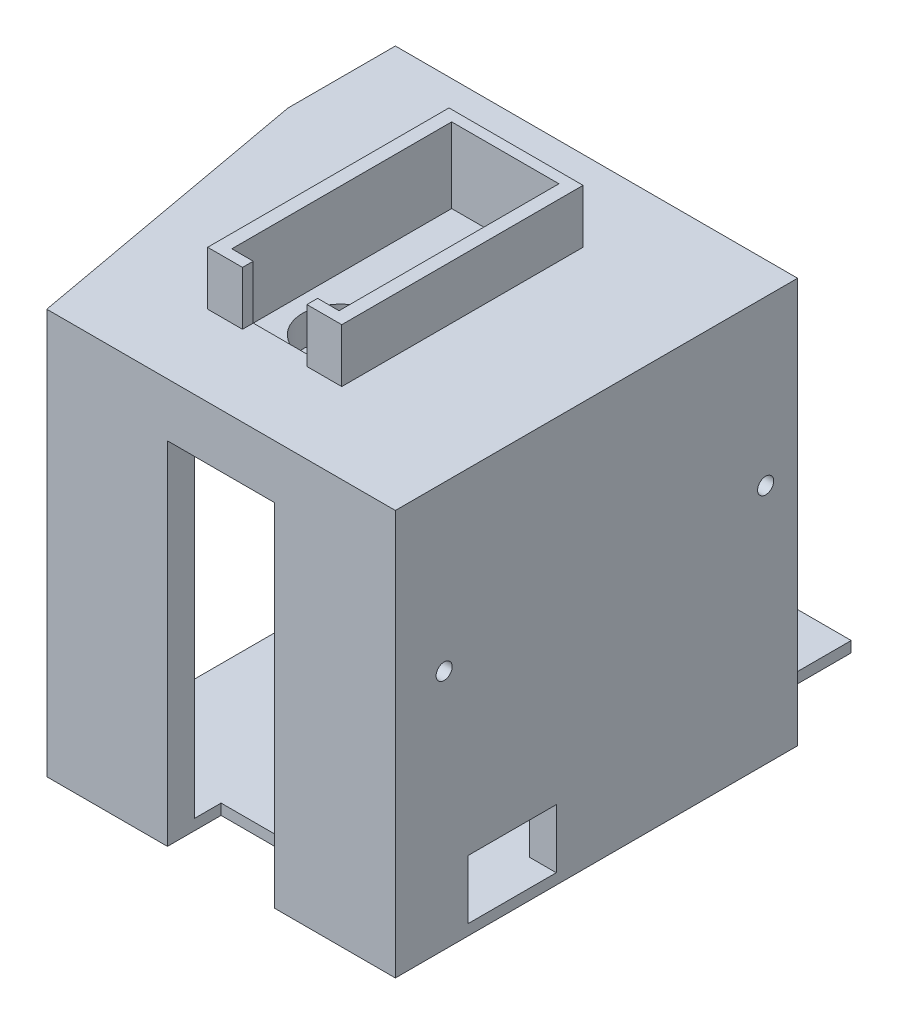
SolidWorks part; units mm, degrees
ref_plane "Front Plane" through (0, 0, 0) normal (0, 0, 1) x (1, 0, 0)
ref_plane "Top Plane" through (0, 0, 0) normal (0, 1, 0) x (1, 0, 0)
ref_plane "Right Plane" through (0, 0, 0) normal (1, 0, 0) x (0, 0, -1)
sketch "Sketch1" plane through (0, 0, 0) normal (0, 1, 0) x (1, 0, 0)
  line L1 (0, 0) -> (55, 0)
  line L2 (0, 0) -> (0, 65)
  line L3 (0, 65) -> (55, 65)
  line L4 (55, 0) -> (55, 65)
  dimension "D1" = 55
  dimension "D2" = 65
extrude "Base" add sketch "Sketch1" along normal blind 2
sketch "Sketch2" plane through (0, 2, 0) normal (0, 1, 0) x (1, 0, 0)
  line L0 (0, 0) -> (55, 0) construction
  line L2 (55, 65) -> (0, 65) construction
  circle A0 centre (3, 3.5) radius 1.2
  circle A1 centre (52, 3.5) radius 1.2
  circle A2 centre (3, 61.5) radius 1.2
  circle A3 centre (52, 61.5) radius 1.2
  point P12 (27.5, 0)
  dimension "D1" = 2.4
  dimension "D2" = 24.5
  dimension "D3" = 24.5
  dimension "D4" = 58
  dimension "D5" = 3.5
extrude "PiMountScrewHoles" cut sketch "Sketch2" against normal up to surface (2 mm away) up to face at (27.5, 0, -32.5)
sketch "Sketch3" plane through (0, 0, 0) normal (-1, 0, 0) x (0, 0, 1)
  line L0 (-65, 0) -> (0, 0) construction
  line L1 (-65, 2) -> (-45, 2)
  line L2 (-65, 2) -> (-65, 0)
  line L3 (-65, 0) -> (-45, 0)
  line L4 (-45, 2) -> (-45, 0)
  dimension "D1" = 20
extrude "PlateLegExt-1" add sketch "Sketch3" along normal blind 10
sketch "Sketch19" plane through (0, 0, -65) normal (0, 0, -1) x (-1, 0, 0)
  line L1 (-55, 2) -> (0, 2)
  line L2 (-55, 2) -> (-55, 0)
  line L3 (-55, 0) -> (0, 0)
  line L4 (0, 2) -> (0, 0)
extrude "PiFrontBase" add sketch "Sketch19" along normal blind 20
sketch "Sketch21" plane through (55, 0, 0) normal (1, 0, 0) x (0, 0, -1)
  line L0 (0, 0) -> (85, 0) construction
  line L1 (0, 2) -> (65, 2)
  line L2 (0, 2) -> (0, 0)
  line L3 (0, 0) -> (65, 0)
  line L4 (65, 2) -> (65, 0)
extrude "BatteryWall-Ext" add sketch "Sketch21" along normal blind 10
sketch "Sketch22" plane through (0, 0, 0) normal (0, 0, 1) x (1, 0, 0)
  line L0 (0, 0) -> (65, 0) construction
  line L1 (0, 2) -> (22.5, 2)
  line L2 (0, 2) -> (0, 0)
  line L3 (0, 0) -> (22.5, 0)
  line L4 (22.5, 2) -> (22.5, 0)
  line L6 (42.5, 2) -> (55, 2)
  line L7 (42.5, 2) -> (42.5, 0)
  line L8 (42.5, 0) -> (55, 0)
  line L11 (0, 2) -> (65, 2) construction
  line L12 (55, 2) -> (55, 0)
  line L13 (55, 0) -> (55, 2) construction
  point P16 (32.5, 0)
  dimension "D1" = 10
  dimension "D2" = 20
extrude "PlateLegExt-2" add sketch "Sketch22" along normal blind 10
sketch "Sketch30" plane through (55, 0, 0) normal (1, 0, 0) x (0, 0, -1)
  line L1 (-10, 2) -> (0, 2)
  line L2 (-10, 2) -> (-10, 0)
  line L3 (-10, 0) -> (0, 0)
  line L4 (0, 2) -> (0, 0)
extrude "CornerExtension" add sketch "Sketch30" along normal up to vertex (10 mm away) up to point (65, 2, 0)
sketch "Sketch23" plane through (0, 2, 0) normal (0, 1, 0) x (1, 0, 0)
  line L0 (65, 65) -> (55, 65) construction
  line L2 (22.5, -5) -> (0, -5)
  line L3 (22.5, -5) -> (22.5, -10)
  line L4 (-5, 65) -> (-10, 65)
  line L8 (60, 65) -> (65, 65)
  line L9 (60, 65) -> (60, -5)
  line L11 (65, 65) -> (65, -10)
  line L14 (-5, 65) -> (-5, 45)
  line L15 (-5, 45) -> (-10, 45)
  line L16 (-10, 65) -> (-10, 45)
  line L21 (22.5, -10) -> (0, -10)
  line L22 (0, -5) -> (0, -10)
  line L23 (22.5, -10) -> (22.5, 0) construction
  line L24 (0, 65) -> (-10, 65) construction
  line L25 (42.5, -10) -> (42.5, 0) construction
  line L26 (42.5, -10) -> (65, -10)
  line L27 (42.5, -10) -> (42.5, -5)
  line L30 (65, 65) -> (65, -10) construction
  line L31 (65, -10) -> (42.5, -10) construction
  line L32 (42.5, -5) -> (60, -5)
extrude "PlateLegs" add sketch "Sketch23" along normal blind 63.5
sketch "Sketch29" plane through (65, 0, 0) normal (1, 0, 0) x (0, 0, -1)
  line L0 (-10, 0) -> (65, 0) construction
  circle A0 centre (59.045, 45) radius 1.5
  circle A1 centre (-0.905, 45) radius 1.5
  point P8 (27.5, 0)
  dimension "D1" = 3
  dimension "D2" = 59.95
  dimension "D3" = 31.545
  dimension "D4" = 45
extrude "Battery-ScrewHoles" cut sketch "Sketch29" against normal up to surface (5 mm away) up to face at (60, 33.75, -30)
sketch "Sketch24" plane through (0, 65.5, 0) normal (0, 1, 0) x (1, 0, 0)
  line L7 (0, -10) -> (65, -10)
  line L8 (42.5, -10) -> (65, -10) construction
  line L9 (65, -10) -> (65, 65)
  line L10 (65, 65) -> (-10, 65)
  line L11 (-10, 65) -> (-10, 45)
  line L12 (-10, 45) -> (0, -10)
extrude "RotatorPlate" add sketch "Sketch24" along normal blind 10
sketch "Sketch25" plane through (0, 75.5, 0) normal (0, 1, 0) x (1, 0, 0)
  line L2 (37.5, 7) -> (37.5, 48)
  line L4 (17.5, 7) -> (17.5, 48)
  line L7 (37.5, 48) -> (17.5, 48)
  line L8 (17.5, 7) -> (37.5, 7)
  line L9 (65, -10) -> (65, 65) construction
  line L11 (65, 65) -> (-10, 65) construction
  point P8 (27.5, 65)
  point P9 (65, 27.5)
  point P10 (37.5, 27.5)
  point P11 (27.5, 48)
  dimension "D1" = 41
  dimension "D2" = 20
extrude "Inset-Servo" cut sketch "Sketch25" against normal blind 4
sketch "Sketch26" plane through (0, 71.5, 0) normal (0, 1, 0) x (1, 0, 0)
  line L0 (17.5, 7) -> (37.5, 7) construction
  line L3 (37.5, 48) -> (17.5, 48) construction
  circle A0 centre (27.5, 17.25) radius 1.5
  point P8 (27.5, 48)
  dimension "D1" = 3
  dimension "D2" = 10.25
extrude "Hole-ServoScrew" cut sketch "Sketch26" against normal up to surface (6 mm away) up to face at (20.9091, 65.5, -15.4545)
sketch "Sketch27" plane through (0, 71.5, 0) normal (0, 1, 0) x (1, 0, 0)
  circle A0 centre (27.5, 17.25) radius 7
  circle A1 centre (27.5, 17.25) radius 1.5 construction
  dimension "D1" = 14
extrude "Inset-ServoAxle" cut sketch "Sketch27" against normal blind 5.8
sketch "Sketch28" plane through (0, 75.5, 0) normal (0, 1, 0) x (1, 0, 0)
  line L2 (37.5, 7) -> (37.5, 48)
  line L4 (17.5, 7) -> (17.5, 48)
  line L6 (40, 5) -> (40, 50)
  line L8 (15, 5) -> (15, 50)
  line L11 (37.5, 7) -> (37.5, 48) construction
  line L18 (17.5, 48) -> (17.5, 7) construction
  line L19 (15, 5) -> (21.5, 5)
  line L24 (21.5, 5) -> (21.5, 7)
  line L25 (17.5, 7) -> (37.5, 7) construction
  line L26 (40, 5) -> (33.5, 5)
  line L27 (33.5, 5) -> (33.5, 7)
  line L28 (17.5, 7) -> (37.5, 7) construction
  line L29 (33.5, 7) -> (37.5, 7)
  line L30 (17.5, 7) -> (21.5, 7)
  line L31 (17.5, 48) -> (37.5, 48)
  line L32 (15, 50) -> (40, 50)
  line L33 (37.5, 48) -> (17.5, 48) construction
  point P15 (27.5, 7)
  point P20 (40, 27.5)
  point P21 (37.5, 27.5)
  dimension "D7" = 6
  dimension "D1" = 2.5
  dimension "D3" = 45
  dimension "D4" = 25
  dimension "D8" = 12
extrude "RetainingWalls-Servo" add sketch "Sketch28" along normal blind 10
sketch "PowerPlug-EdgeLine" plane through (0, 2, 0) normal (0, 1, 0) x (1, 0, 0)
  line L1 (52, 3.5) -> (60, 3.5) construction
  line L3 (60, 65) -> (60, -5) construction
sketch "Sketch31" plane through (60, 0, 0) normal (-1, 0, 0) x (0, 0, 1)
  line L0 (-65, 2) -> (5, 2) construction
  line L1 (-20, 13) -> (-3.5, 13)
  line L2 (-20, 13) -> (-20, 2)
  line L3 (-20, 2) -> (-3.5, 2)
  line L4 (-3.5, 13) -> (-3.5, 2)
  line L6 (5, 65.5) -> (5, 2) construction
  point P8 (0, 0)
  point P9 (-3.4479, 2)
  point P10 (0, 0)
  dimension "D2" = 11
  dimension "D3" = 25
extrude "Power-Hole" cut sketch "Sketch31" against normal up to surface (5 mm away) up to face at (65, 45, -60.545)
equation "\"PlateLegExtent\"= 10mm"
equation "\"D1@PlateLegExt-1\" = \"PlateLegExtent\""
equation "\"PlateLegHeight\"= 2.5in"
equation "\"D1@BatteryWall-Ext\" = \"PlateLegExtent\""
equation "\"D1@PlateLegExt-2\" = \"PlateLegExtent\""
equation "\"D1@PlateLegs\" = \"PlateLegHeight\""
